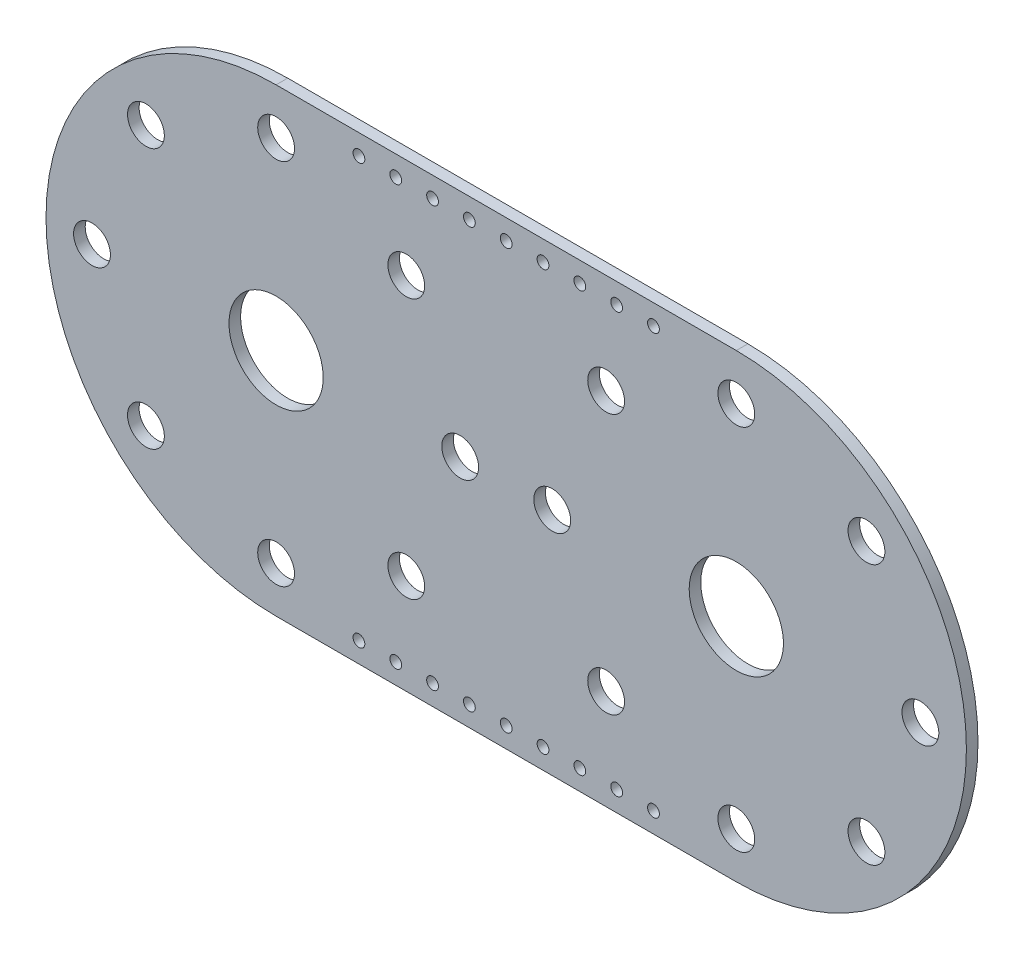
SolidWorks part; units mm, degrees
ref_plane "Front Plane" through (0, 0, 0) normal (0, 0, 1) x (1, 0, 0)
ref_plane "Top Plane" through (0, 0, 0) normal (0, 1, 0) x (1, 0, 0)
ref_plane "Right Plane" through (0, 0, 0) normal (1, 0, 0) x (0, 0, -1)
sketch "Sketch1" plane through (0, 0, 0) normal (0, 0, 1) x (1, 0, 0)
  line L0 (-15.875, 15.875) -> (47.625, 15.875) construction
  line L3 (0, 31.75) -> (31.75, 31.75)
  line L5 (0, 0) -> (31.75, 0)
  line L7 (15.875, 31.75) -> (15.875, 0) construction
  arc A40 (0, 31.75) -> (0, 0) centre (0, 15.875) ccw
  arc A41 (31.75, 0) -> (31.75, 31.75) centre (31.75, 15.875) ccw
  circle A42 centre (0, 15.875) radius 3.2512
  circle A43 centre (31.75, 15.875) radius 3.2512
  circle A44 centre (-12.7, 15.875) radius 1.27
  circle A45 centre (-8.9803, 24.8553) radius 1.27
  circle A46 centre (0, 28.575) radius 1.27
  circle A47 centre (8.9803, 24.8553) radius 1.27
  circle A48 centre (12.7, 15.875) radius 1.27
  circle A49 centre (8.9803, 6.8947) radius 1.27
  circle A50 centre (0, 3.175) radius 1.27
  circle A51 centre (-8.9803, 6.8947) radius 1.27
  circle A52 centre (31.75, 3.175) radius 1.27
  circle A53 centre (40.7303, 6.8947) radius 1.27
  circle A54 centre (22.7697, 6.8947) radius 1.27
  circle A55 centre (19.05, 15.875) radius 1.27
  circle A56 centre (22.7697, 24.8553) radius 1.27
  circle A57 centre (31.75, 28.575) radius 1.27
  circle A58 centre (40.7303, 24.8553) radius 1.27
  circle A59 centre (44.45, 15.875) radius 1.27
  point P29 (0, 15.875)
  dimension "D2" = 31.75
  dimension "D4" = 6.5024
  dimension "D5" = 12.7
  dimension "D6" = 8
  dimension "D1" = 31.75
  dimension "D3" = 6.5024
extrude "Boss-Extrude1" add sketch "Sketch1" along normal blind 0.8 contours L5 A41 L3 A40 A58 A56 A54 A52 A51 A50 A49 A48 A47 A46 A45 A44 A43 A42 A53 A55 A57 A59 region at (15.875, 15.875, 0)
sketch "Sketch3" plane through (0, 0, 0.8) normal (0, 0, -1) x (-1, 0, 0)
  line L0 (0, 0) -> (-31.75, 0) construction
  line L2 (0, 31.75) -> (-31.75, 31.75) construction
  line L3 (0, 0) -> (-31.75, 0)
  line L4 (0, 31.75) -> (-31.75, 31.75)
  line L5 (-15.875, 31.75) -> (-15.875, 0) construction
  line L6 (0, 15.875) -> (-33.3089, 15.875) construction
  circle A16 centre (-13.335, 30.353) radius 0.4064
  circle A17 centre (-10.795, 30.353) radius 0.4064
  circle A18 centre (-8.255, 30.353) radius 0.4064
  circle A19 centre (-5.715, 30.353) radius 0.4064
  circle A20 centre (-26.035, 30.353) radius 0.4064
  circle A21 centre (-23.495, 30.353) radius 0.4064
  circle A22 centre (-20.955, 30.353) radius 0.4064
  circle A23 centre (-18.415, 30.353) radius 0.4064
  circle A24 centre (-18.415, 1.397) radius 0.4064
  circle A25 centre (-20.955, 1.397) radius 0.4064
  circle A26 centre (-23.495, 1.397) radius 0.4064
  circle A27 centre (-26.035, 1.397) radius 0.4064
  circle A28 centre (-5.715, 1.397) radius 0.4064
  circle A29 centre (-8.255, 1.397) radius 0.4064
  circle A30 centre (-10.795, 1.397) radius 0.4064
  circle A31 centre (-13.335, 1.397) radius 0.4064
  circle A32 centre (-15.875, 30.353) radius 0.4064
  circle A33 centre (-15.875, 1.397) radius 0.4064
  dimension "D1" = 30.353
  dimension "D2" = 0.8128
  dimension "D4" = 0.8128
  dimension "D3" = 2.54
extrude "Cut-Extrude3" cut sketch "Sketch3" along normal through all contours A33 | A32 | A19 | A18 | A17 | A16 | A23 | A22 | A21 | A20 | A28 | A29 | A30 | A31 | A24 | A25 | A26 | A27 region at (15.875, 30.353, 0.8) region at (15.875, 1.397, 0.8)
